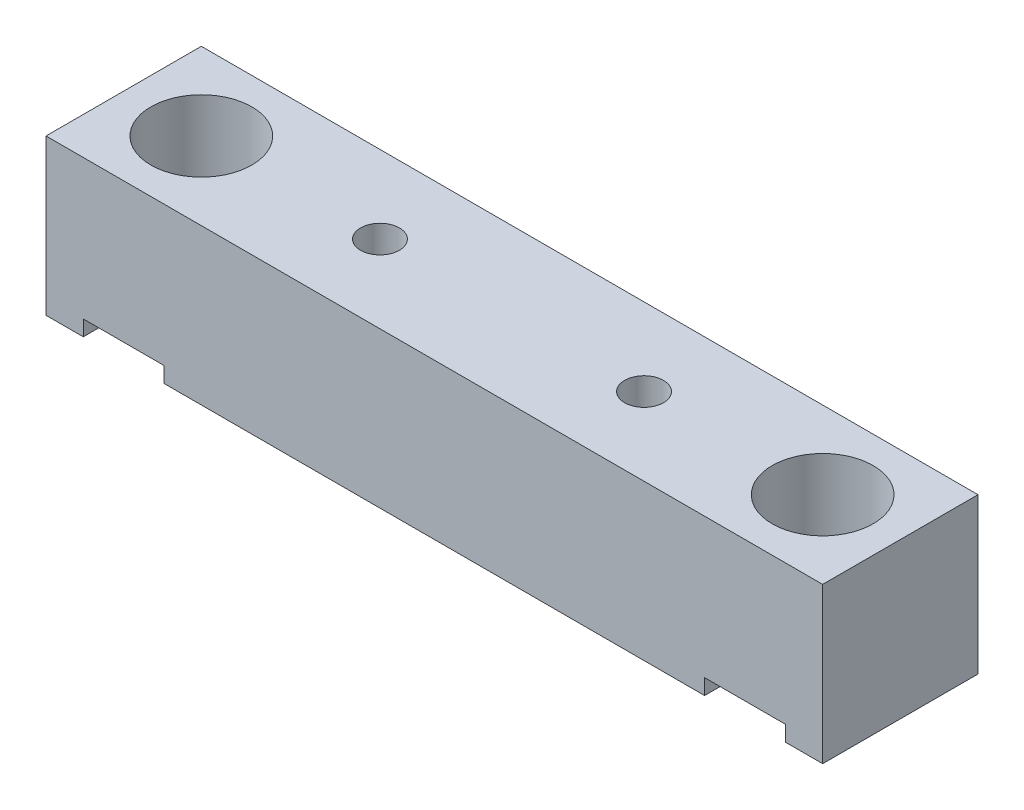
SolidWorks part; units mm, degrees
ref_plane "Front Plane" through (0, 0, 0) normal (0, 0, 1) x (1, 0, 0)
ref_plane "Top Plane" through (0, 0, 0) normal (0, 1, 0) x (1, 0, 0)
ref_plane "Right Plane" through (0, 0, 0) normal (1, 0, 0) x (0, 0, -1)
sketch "Sketch1" plane through (0, 0, 0) normal (0, 1, 0) x (1, 0, 0)
  line L1 (-25, -5) -> (25, -5)
  line L2 (-25, -5) -> (-25, 5)
  line L3 (-25, 5) -> (25, 5)
  line L4 (25, -5) -> (25, 5)
  line L5 (-25, -5) -> (25, 5) construction
  line L6 (-25, 5) -> (25, -5) construction
  point P0 (0, 0)
  dimension "D1" = 50
  dimension "D2" = 10
extrude "Boss-Extrude1" add sketch "Sketch1" along normal blind 10
sketch "Sketch2" plane through (0, 0, 5) normal (0, 0, 1) x (1, 0, 0)
  line L0 (-25, 0) -> (25, 0) construction
  line L1 (17.4, 0) -> (22.6, 0)
  line L2 (17.4, 0) -> (17.4, 1)
  line L3 (17.4, 1) -> (22.6, 1)
  line L4 (22.6, 0) -> (22.6, 1)
  line L5 (17.4, 0) -> (22.6, 1) construction
  line L6 (17.4, 1) -> (22.6, 0) construction
  point P0 (20, 0.5)
  point P5 (0, 0)
  dimension "D1" = 5.2
  dimension "D2" = 1
  dimension "D3" = 20
extrude "Cut-Extrude1" cut sketch "Sketch2" against normal blind 10
hole_wizard "CBORE for M3 SHCS1" positions "Sketch3" profile "Sketch5" counterbore size "M3" standard "ANSI Metric" end condition through all
sketch "Sketch3" plane through (0, 10, 0) normal (0, 1, 0) x (1, 0, 0)
  point P0 (20, 0)
  dimension "D1" = 20
sketch "Sketch5" plane through (20, 10, 0) normal (1, 0, 0) x (0, 0, 1)
  line L0 (0, 0) -> (0, 10)
  line L1 (0, 10) -> (1.7, 10)
  line L3 (1.7, 10) -> (1.7, 6)
  line L4 (1.7, 6) -> (3.25, 6)
  line L5 (3.25, 6) -> (3.25, 0)
  line L7 (3.25, 0) -> (0, 0)
  line L11 (0, -6.35) -> (0, 107.95) construction
  dimension "Thru Hole Dia." = 3.4
  dimension "Thru Hole Depth" = 10
  dimension "C'Bore Dia." = 6.5
  dimension "C'Bore Depth" = 6
mirror "Mirror1" about plane through (0, 0, 0) normal (1, 0, 0) of "CBORE for M3 SHCS1", "Cut-Extrude1"
hole_wizard "M3x0.5 Tapped Hole1" positions "Sketch6" profile "Sketch8" tap size "M3x0.5" standard "ANSI Metric"
sketch "Sketch6" plane through (0, 10, 0) normal (0, 1, 0) x (1, 0, 0)
  line L0 (-8.5, 0) -> (8.5, 0)
  point P1 (-8.5, 0)
  point P2 (8.5, 0)
  point P5 (0, 0)
  dimension "D1" = 17
sketch "Sketch8" plane through (-8.5, 10, 0) normal (1, 0, 0) x (0, 0, 1)
  line L0 (0, 0) -> (0, 8.2511)
  line L1 (0, 8.2511) -> (1.25, 7.5)
  line L2 (1.25, 7.5) -> (1.25, 0)
  line L5 (1.25, 0) -> (0, 0)
  line L10 (0, 8.2511) -> (-1.25, 7.5) construction
  line L11 (0, -6.35) -> (0, 107.95) construction
  dimension "Tap Drill Dia." = 2.5
  dimension "Tap Drill Depth" = 7.5
  dimension "Drill Angle" = 118
cosmetic thread "Hole Thread1" parameters "D1"=6, "D2"=3
cosmetic thread "Hole Thread2" parameters "D1"=6, "D2"=3
